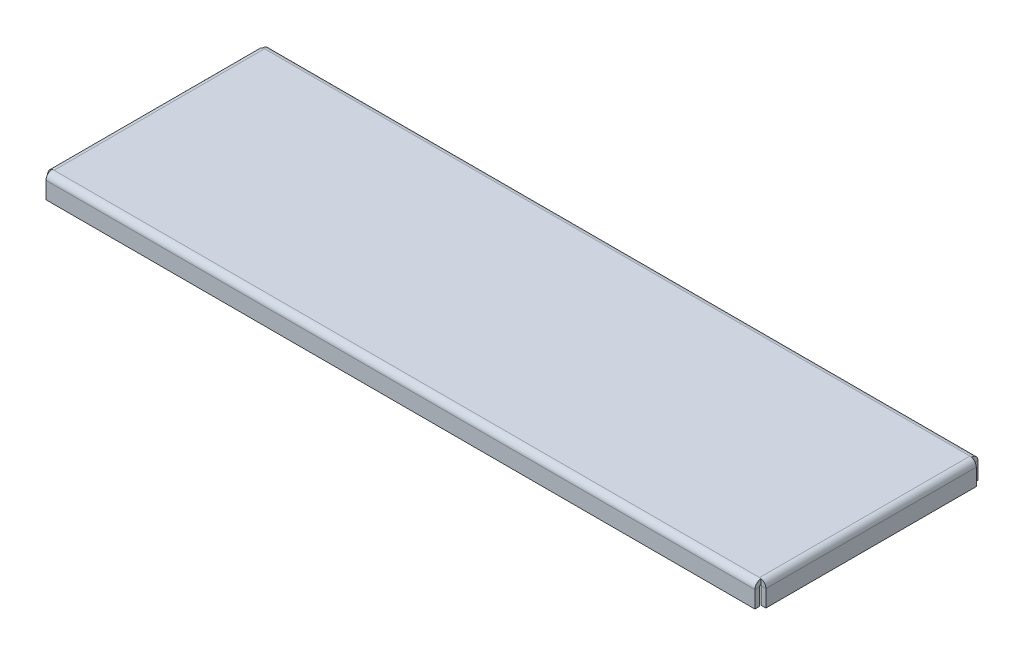
SolidWorks part; units mm, degrees
note: The reader was unsure of these and kept them because the rebuilt part matched: flange length of "Edge-Flange1", "Edge-Flange2", "Edge-Flange3", "Edge-Flange4".
material "ASTM A36 Steel"
ref_plane "Front Plane" through (0, 0, 0) normal (0, 0, 1) x (1, 0, 0)
ref_plane "Top Plane" through (0, 0, 0) normal (0, 1, 0) x (1, 0, 0)
ref_plane "Right Plane" through (0, 0, 0) normal (1, 0, 0) x (0, 0, -1)
sketch "Sketch1" plane through (0, 0, 0) normal (0, 0, 1) x (1, 0, 0)
  line L1 (-152.5, 5) -> (152.5, 5)
  line L2 (-152.5, 5) -> (-152.5, -5)
  line L3 (-152.5, -5) -> (152.5, -5)
  line L4 (152.5, 5) -> (152.5, -5)
  dimension "D1" = 10
  dimension "D2" = 305
  dimension "D3" = 152.5
  dimension "D4" = 5
base flange "Base-Flange3" sketch "Sketch1" thickness 2 reverse thickness direction no parameters "D1"=0.7366
edge flange "Edge-Flange1" sketch "Sketch4" flange angle 90 flange length 96 flange position material inside bend radius 0.7366 thickness 2 relief rectangular parameters "D6"=10
sketch "Sketch4" plane through (0, 5, -2) normal (0, 1, 0) x (1, 0, 0)
  line L0 (152.5, 0) -> (-152.5, 0) construction
  line L1 (152.5, 0) -> (-152.5, 0)
  line L2 (-152.5, 0) -> (-152.5, 94)
  line L3 (-152.5, 94) -> (152.5, 94)
  line L4 (152.5, 94) -> (152.5, 0)
bend "EdgeBend1" bend radius 0.7366 bend angle 90 parameters "D5"=1
edge flange "Edge-Flange2" sketch "Sketch7" flange angle 90 flange length 10 flange position material inside bend radius 0.7366 thickness 2 relief rectangular parameters "D6"=10
sketch "Sketch7" plane through (0, 3, -96) normal (0, 0, -1) x (1, 0, 0)
  line L0 (152.5, 0) -> (-152.5, 0) construction
  line L1 (152.5, 0) -> (-152.5, 0)
  line L2 (-152.5, 0) -> (-152.5, 8)
  line L3 (-152.5, 8) -> (152.5, 8)
  line L4 (152.5, 8) -> (152.5, 0)
bend "EdgeBend2" bend radius 0.7366 bend angle 90 parameters "D5"=2
edge flange "Edge-Flange3" sketch "Sketch10" flange angle 90 flange length 10 flange position material outside bend radius 0.7366 thickness 2 relief none parameters "D6"=10
sketch "Sketch10" plane through (-152.5, 3, 0) normal (-1, 0, 0) x (0, 0, -1)
  line L2 (2.7366, 0) -> (2.7366, 8)
  line L3 (2.7366, 8) -> (93.2634, 8)
  line L4 (93.2634, 8) -> (93.2634, 0)
  line L7 (93.2634, 0) -> (2.7366, 0) construction
  line L8 (93.2634, 0) -> (2.7366, 0)
bend "EdgeBend3" bend radius 0.7366 bend angle 90 parameters "D5"=3
edge flange "Edge-Flange4" sketch "Sketch13" flange angle 90 flange length 10 flange position material outside bend radius 0.7366 thickness 2 relief none parameters "D6"=10
sketch "Sketch13" plane through (152.5, 3, 0) normal (1, 0, 0) x (0, 0, 1)
  line L0 (-2.7366, 0) -> (-93.2634, 0) construction
  line L1 (-2.7366, 0) -> (-93.2634, 0)
  line L2 (-93.2634, 0) -> (-93.2634, 8)
  line L3 (-93.2634, 8) -> (-2.7366, 8)
  line L4 (-2.7366, 8) -> (-2.7366, 0)
bend "EdgeBend4" bend radius 0.7366 bend angle 90 parameters "D5"=4
sketch "Sketch14" plane through (0, 3, 0) normal (0, -1, 0) x (1, 0, 0)
  circle A0 centre (116.1, -97.5) radius 1.6
  circle A1 centre (-70.5, -97.5) radius 1.6
  circle A2 centre (112.9, -6.5) radius 1.6
  circle A3 centre (59.99, -6.5) radius 1.6
  circle A5 centre (-70.5, -6.5) radius 1.6
sketch "Bend-Lines5" [suppressed] plane through (0, 0, 0) normal (0, 1, 0) x (1, 0, 0)
sketch "Bounding-Box5" [suppressed] plane through (0, 0, 0) normal (0, 1, 0) x (1, 0, 0)
sheet metal parameters "Sheet-Metal3" thickness 2 parameters "D1"=0.7366
flat pattern "Flat-Pattern3" [suppressed]
sketch "Bend-Lines6" plane through (0, 0, 0) normal (0, 1, 0) x (1, 0, 0)
sketch3d "Bounding-Box6" [suppressed]
  line L0 (-154.5, -5, 0) -> (154.5, -5, 0) construction
  line L1 (-154.5, 5, 0) -> (154.5, 5, 0) construction
  line L2 (-154.5, -5, 0) -> (-154.5, 5, 0) construction
  line L3 (154.5, -5, 0) -> (154.5, 5, 0) construction
sheet metal parameters "Sheet-Metal8" thickness 2 parameters "D1"=0.7366
flat pattern "Flat-Pattern3"
sketch "Bend-Lines6" plane through (0, 0, 0) normal (0, 0, 1) x (1, 0, 0)
  line L0 (154.5, 3.6273) -> (-154.5, 3.6273) construction
  line L1 (154.5, 3.6273) -> (-154.5, 3.6273) construction
sketch3d "Bounding-Box6" [suppressed]
  line L0 (-154.5, -5, 0) -> (154.5, -5, 0) construction
  line L1 (-154.5, 98.2546, 0) -> (154.5, 98.2546, 0) construction
  line L2 (-154.5, -5, 0) -> (-154.5, 98.2546, 0) construction
  line L3 (154.5, -5, 0) -> (154.5, 98.2546, 0) construction
bend of the flat pattern "Flatten-<EdgeBend1>1"
sheet metal parameters "Sheet-Metal9" thickness 2 parameters "D1"=0.7366
flat pattern "Flat-Pattern3"
sketch "Bend-Lines6" plane through (0, 0, 0) normal (0, 0, 1) x (1, 0, 0)
  line L0 (154.5, 3.6273) -> (-154.5, 3.6273) construction
  line L1 (154.5, 3.6273) -> (-154.5, 3.6273) construction
  line L2 (154.5, 96.882) -> (-154.5, 96.882) construction
  line L3 (154.5, 96.882) -> (-154.5, 96.882) construction
sketch3d "Bounding-Box6" [suppressed]
  line L0 (-154.5, -5, 0) -> (154.5, -5, 0) construction
  line L1 (-154.5, 105.5093, 0) -> (154.5, 105.5093, 0) construction
  line L2 (-154.5, -5, 0) -> (-154.5, 105.5093, 0) construction
  line L3 (154.5, -5, 0) -> (154.5, 105.5093, 0) construction
bend of the flat pattern "Flatten-<EdgeBend1>1"
bend of the flat pattern "Flatten-<EdgeBend2>1"
sheet metal parameters "Sheet-Metal10" thickness 2 parameters "D1"=0.7366
flat pattern "Flat-Pattern3"
sketch "Bend-Lines6" plane through (0, 0, 0) normal (0, 0, 1) x (1, 0, 0)
  line L0 (-154.5, 3.6273) -> (154.5, 3.6273) construction
  line L1 (-154.5, 3.6273) -> (154.5, 3.6273) construction
  line L2 (154.5, 96.882) -> (-154.5, 96.882) construction
  line L3 (154.5, 96.882) -> (-154.5, 96.882) construction
  line L4 (-153.1273, 95.518) -> (-153.1273, 4.9912) construction
  line L5 (-153.1273, 95.518) -> (-153.1273, 4.9912) construction
sketch3d "Bounding-Box6" [suppressed]
  line L0 (-161.7546, -5, 0) -> (154.5, -5, 0) construction
  line L1 (-161.7546, 105.5093, 0) -> (154.5, 105.5093, 0) construction
  line L2 (-161.7546, -5, 0) -> (-161.7546, 105.5093, 0) construction
  line L3 (154.5, -5, 0) -> (154.5, 105.5093, 0) construction
bend of the flat pattern "Flatten-<EdgeBend1>1"
bend of the flat pattern "Flatten-<EdgeBend2>1"
bend of the flat pattern "Flatten-<EdgeBend3>1"
sheet metal parameters "Sheet-Metal11" thickness 2 parameters "D1"=0.7366
flat pattern "Flat-Pattern3"
sketch "Bend-Lines6" plane through (0, 0, 0) normal (0, 0, 1) x (1, 0, 0)
  line L0 (-152.5, 3.6273) -> (152.5, 3.6273) construction
  line L1 (-152.5, 3.6273) -> (152.5, 3.6273) construction
  line L2 (152.5, 96.882) -> (-152.5, 96.882) construction
  line L3 (152.5, 96.882) -> (-152.5, 96.882) construction
  line L4 (-153.1273, 95.518) -> (-153.1273, 4.9912) construction
  line L5 (-153.1273, 95.518) -> (-153.1273, 4.9912) construction
  line L6 (153.1273, 4.9912) -> (153.1273, 95.518) construction
  line L7 (153.1273, 4.9912) -> (153.1273, 95.518) construction
sketch3d "Bounding-Box6" [suppressed]
  line L0 (-161.7546, -5, 0) -> (161.7546, -5, 0) construction
  line L1 (-161.7546, 105.5093, 0) -> (161.7546, 105.5093, 0) construction
  line L2 (-161.7546, -5, 0) -> (-161.7546, 105.5093, 0) construction
  line L3 (161.7546, -5, 0) -> (161.7546, 105.5093, 0) construction
bend of the flat pattern "Flatten-<EdgeBend1>1"
bend of the flat pattern "Flatten-<EdgeBend2>1"
bend of the flat pattern "Flatten-<EdgeBend3>1"
bend of the flat pattern "Flatten-<EdgeBend4>1"
